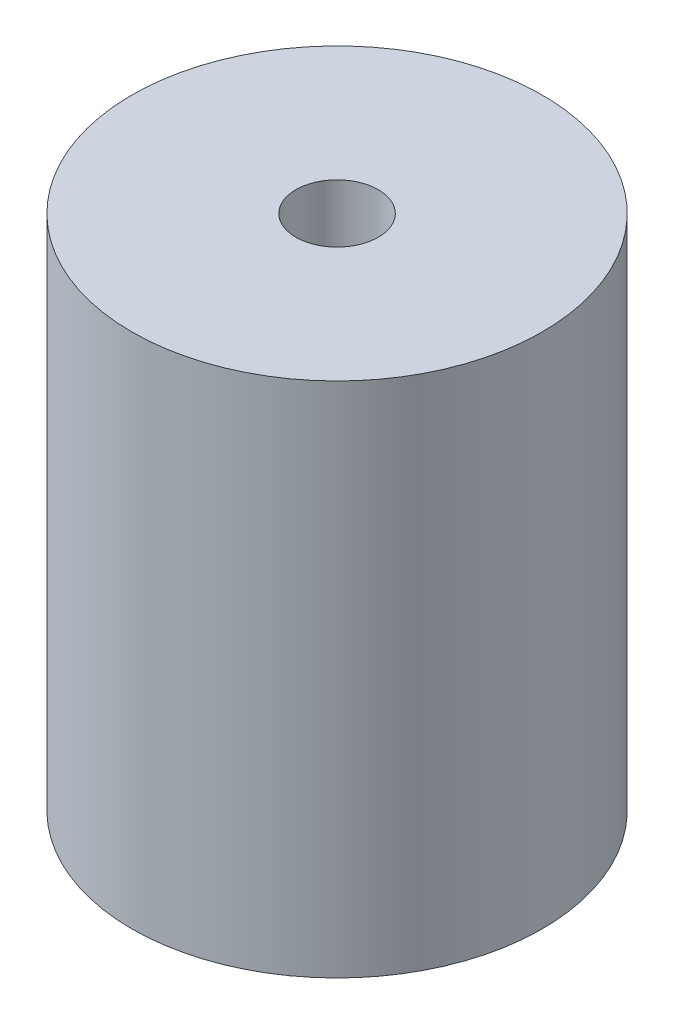
SolidWorks part; units mm, degrees
material "Delrin 2700 NC010, Low Viscosity Acetal Copolymer (SS)"
ref_plane "Front Plane" through (0, 0, 0) normal (0, 0, 1) x (1, 0, 0)
ref_plane "Top Plane" through (0, 0, 0) normal (0, 1, 0) x (1, 0, 0)
ref_plane "Right Plane" through (0, 0, 0) normal (1, 0, 0) x (0, 0, -1)
sketch "Sketch1" plane through (0, 0, 0) normal (0, 1, 0) x (1, 0, 0)
  circle A0 centre (0, 0) radius 12.7
  dimension "D1" = 25.4
extrude "Boss-Extrude1" add sketch "Sketch1" along normal blind 32
sketch "Sketch2" plane through (0, 0, 0) normal (0, -1, 0) x (1, 0, 0)
  point P0 (0, 0)
hole_wizard "Tap Drill for 1/4-20 Tap1" positions "Sketch2" profile "Sketch3" hole size "1/4-20" standard "ANSI Inch"
sketch "Sketch3" plane through (0, 0, 0) normal (1, 0, 0) x (0, 0, -1)
  line L0 (0, 0) -> (0, 11.6938)
  line L1 (0, 11.6938) -> (2.5527, 10.16)
  line L2 (2.5527, 10.16) -> (2.5527, 0)
  line L5 (2.5527, 0) -> (0, 0)
  line L10 (0, 11.6938) -> (-2.5527, 10.16) construction
  line L11 (0, -6.35) -> (0, 107.95) construction
  dimension "Hole Dia." = 5.1054
  dimension "Hole Depth" = 10.16
  dimension "Drill Angle" = 118
sketch "Sketch4" plane through (0, 32, 0) normal (0, 1, 0) x (1, 0, 0)
  point P0 (0, 0)
hole_wizard "Tap Drill for 1/4-20 Tap2" positions "Sketch4" profile "Sketch5" hole size "1/4-20" standard "ANSI Inch"
sketch "Sketch5" plane through (0, 32, 0) normal (1, 0, 0) x (0, 0, 1)
  line L0 (0, 0) -> (0, 11.6938)
  line L1 (0, 11.6938) -> (2.5527, 10.16)
  line L2 (2.5527, 10.16) -> (2.5527, 0)
  line L5 (2.5527, 0) -> (0, 0)
  line L10 (0, 11.6938) -> (-2.5527, 10.16) construction
  line L11 (0, -6.35) -> (0, 107.95) construction
  dimension "Hole Dia." = 5.1054
  dimension "Hole Depth" = 10.16
  dimension "Drill Angle" = 118
